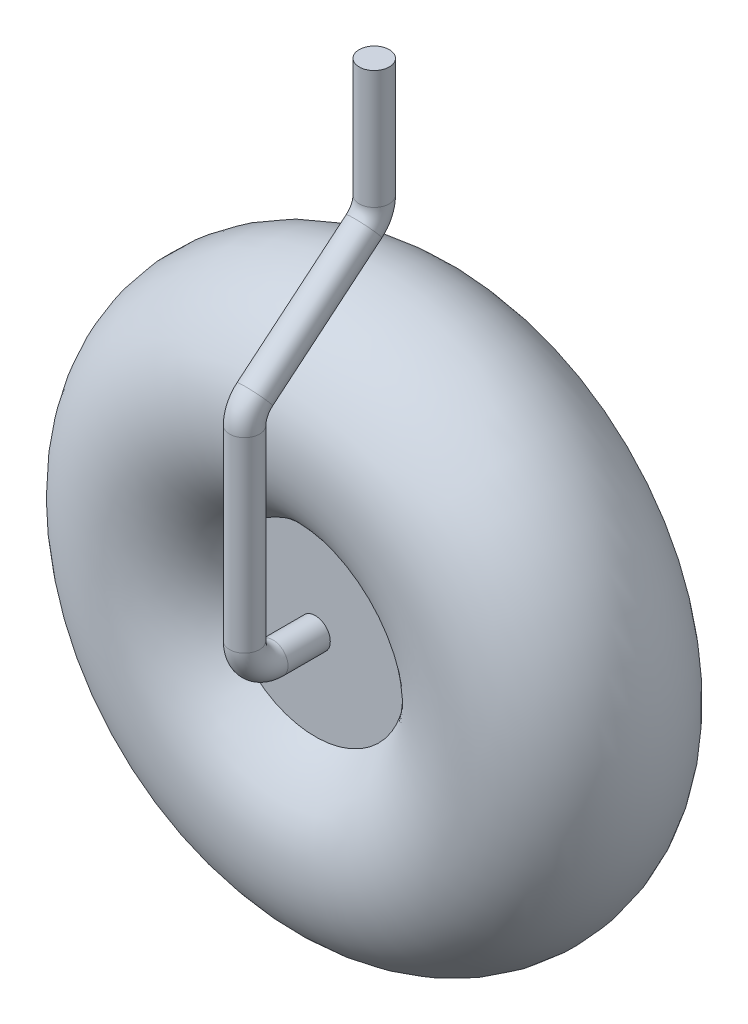
SolidWorks part; units mm, degrees
ref_plane "Front Plane" through (0, 0, 0) normal (0, 0, 1) x (1, 0, 0)
ref_plane "Top Plane" through (0, 0, 0) normal (0, 1, 0) x (1, 0, 0)
ref_plane "Right Plane" through (0, 0, 0) normal (1, 0, 0) x (0, 0, -1)
sketch "Sketch1" plane through (0, 0, 0) normal (1, 0, 0) x (0, 0, -1)
  line L0 (0, 0) -> (0, 25.4) construction
  line L1 (0, 0) -> (-12.9614, 0) construction
  line L2 (-5.2724, 0) -> (5.2724, 0)
  line L3 (-5.2724, -8.0369) -> (5.2724, -8.0369)
  line L4 (-5.2724, -8.0369) -> (-5.2724, 8.0369)
  line L5 (-5.2724, 8.0369) -> (5.2724, 8.0369)
  line L6 (5.2724, -8.0369) -> (5.2724, 8.0369)
  line L7 (-5.2724, -8.0369) -> (5.2724, 8.0369) construction
  line L8 (-5.2724, 8.0369) -> (5.2724, -8.0369) construction
  circle A0 centre (0, 15.918) radius 9.482
  dimension "D1" = 25.4
revolve "Revolve1" add sketch "Sketch1" angle 360 about L1 region at (0, 3.491, 0) region at (0, 16.2785, 0) region at (0, 7.3917, 0)
sketch "Sketch2" plane through (0, 0, 0) normal (1, 0, 0) x (0, 0, -1)
  line L0 (0, 0) -> (-9.0505, 0)
  line L1 (-11.5905, 2.54) -> (-11.5905, 19.2279)
  line L2 (-10.6758, 21.1798) -> (-0.9147, 29.3071)
  line L3 (0, 31.2591) -> (0, 41.8609)
  arc A0 (-0.9147, 29.3071) -> (0, 31.2591) centre (-2.54, 31.2591) ccw
  arc A1 (-11.5905, 19.2279) -> (-10.6758, 21.1798) centre (-9.0505, 19.2279) cw
  arc A2 (-9.0505, 0) -> (-11.5905, 2.54) centre (-9.0505, 2.54) cw
  dimension "D1" = 2.54
sketch "Sketch3" plane through (0, 0, 5.2724) normal (0, 0, 1) x (1, 0, 0)
  circle A0 centre (0, 0) radius 1.3442
sweep "Sweep1" add profiles "Sketch3" path "Sketch2"
